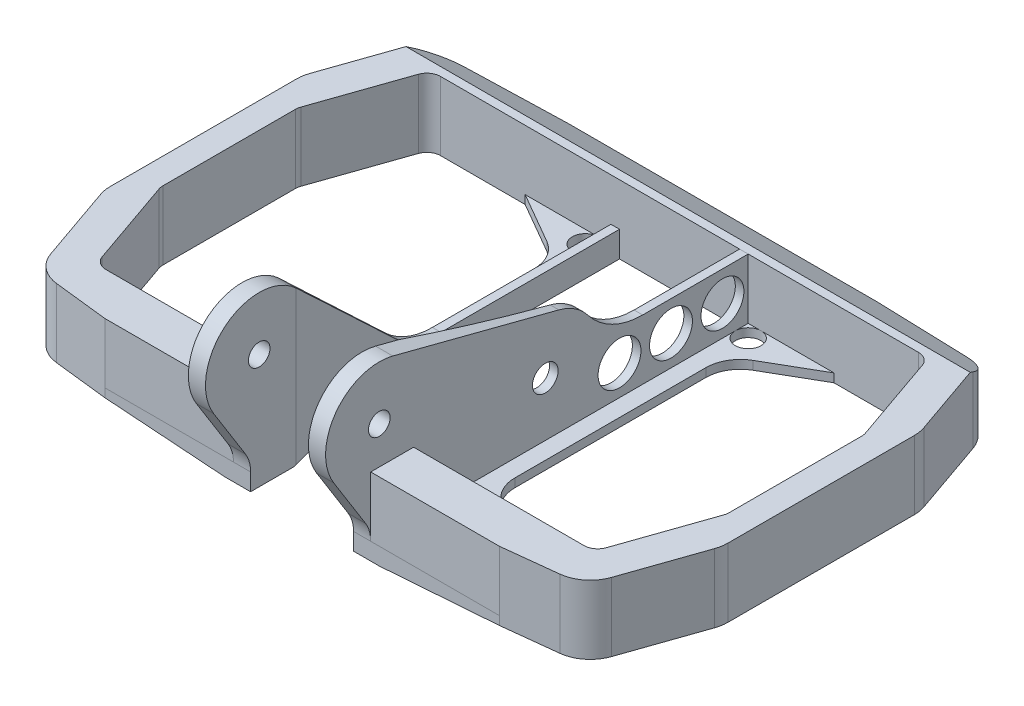
SolidWorks part; units mm, degrees
material "6061 Alloy"
ref_plane "Front Plane" through (0, 0, 0) normal (0, 0, 1) x (1, 0, 0)
ref_plane "Top Plane" through (0, 0, 0) normal (0, 1, 0) x (1, 0, 0)
ref_plane "Right Plane" through (0, 0, 0) normal (1, 0, 0) x (0, 0, -1)
sketch "Sketch1" plane through (0, 0, 0) normal (0, 0, 1) x (1, 0, 0)
  line L0 (19.05, 0) -> (19.05, 76.2)
  line L1 (19.05, 76.2) -> (25.4, 76.2)
  line L2 (25.4, 76.2) -> (25.4, 6.35)
  line L3 (25.4, 6.35) -> (95.25, 6.35)
  line L4 (95.25, 6.35) -> (95.25, 0)
  line L5 (95.25, 0) -> (19.05, 0)
  line L6 (19.05, 0) -> (-19.05, 0) construction
  line L7 (-19.05, 76.2) -> (-19.05, 0)
  line L8 (-19.05, 0) -> (-95.25, 0)
  line L9 (-95.25, 0) -> (-95.25, 6.35)
  line L10 (-95.25, 6.35) -> (-25.4, 6.35)
  line L11 (-25.4, 6.35) -> (-25.4, 76.2)
  line L12 (-25.4, 76.2) -> (-19.05, 76.2)
  point P2 (0, 0)
  dimension "D1" = 76.2
  dimension "D2" = 6.35
  dimension "D3" = 38.1
extrude "Boss-Extrude1" add sketch "Sketch1" against normal blind 203.2
sketch "Sketch4" plane through (25.4, 0, 0) normal (1, 0, 0) x (0, 0, -1)
  line L0 (17.1205, 13.0795) -> (5.3696, 31.8865)
  line L1 (203.2, 0) -> (0, 0) construction
  line L2 (27.2163, 61.6561) -> (88.6811, 45.709)
  line L4 (203.2, 6.35) -> (0, 6.35) construction
  line L5 (19.05, 0) -> (0, 0)
  line L6 (0, 0) -> (0, 76.2)
  line L7 (0, 76.2) -> (203.2, 76.2)
  line L8 (203.2, 76.2) -> (0, 76.2) construction
  line L9 (158.75, 28.575) -> (158.75, 6.35)
  line L10 (158.75, 28.575) -> (103.5343, 28.575)
  line L11 (158.75, 6.35) -> (203.2, 6.35)
  line L12 (203.2, 6.35) -> (203.2, 76.2)
  line L13 (203.2, 0) -> (203.2, 6.35) construction
  line L14 (19.05, 0) -> (19.05, 6.35)
  arc A0 (5.3696, 31.8865) -> (27.2163, 61.6561) centre (22.225, 42.418) cw
  circle A1 centre (22.225, 42.418) radius 4
  circle A2 centre (83.6585, 26.35) radius 20 construction
  arc A3 (88.6811, 45.709) -> (103.5343, 28.575) centre (83.6585, 26.35) cw
  arc A4 (17.1205, 13.0795) -> (19.05, 6.35) centre (6.35, 6.35) cw
  point P27 (19.05, 0)
  point P40 (19.05, 6.35)
  dimension "D1" = 8
  dimension "D3" = 15.875
  dimension "D4" = 40
  dimension "D5" = 63.5
  dimension "D6" = 139.7
  dimension "D9" = 12.7
  dimension "D2" = 42.418
  dimension "D7" = 22.225
  dimension "D8" = 28.575
  dimension "D10" = 3.175
extrude "Cut-Extrude2" cut sketch "Sketch4" against normal through all both and the other way through all
sketch "Sketch7" plane through (-19.05, 0, 0) normal (1, 0, 0) x (0, 0, -1)
  line L0 (17.1205, 13.0795) -> (5.3696, 31.8865)
  line L1 (35.8851, 56.8547) -> (82.55, 12.7)
  line L2 (82.55, 12.7) -> (158.75, 12.7)
  line L3 (158.75, 28.575) -> (158.75, 6.35) construction
  line L4 (158.75, 12.7) -> (158.75, 6.35)
  line L5 (158.75, 6.35) -> (203.2, 6.35)
  line L6 (203.2, 6.35) -> (203.2, 76.2)
  line L7 (203.2, 76.2) -> (0, 76.2)
  line L8 (0, 76.2) -> (0, 0)
  line L9 (0, 0) -> (19.05, 0)
  line L11 (203.2, 0) -> (203.2, 76.2) construction
  line L12 (203.2, 0) -> (203.2, 6.35) construction
  line L13 (203.2, 6.35) -> (19.05, 6.35) construction
  line L14 (19.05, 0) -> (19.05, 6.35) construction
  line L15 (19.05, 0) -> (19.05, 6.35)
  line L16 (103.5343, 28.575) -> (158.75, 28.575) construction
  arc A0 (5.3696, 31.8865) -> (35.8851, 56.8547) centre (22.225, 42.418) cw
  circle A1 centre (22.225, 42.418) radius 4 construction
  circle A2 centre (22.225, 42.418) radius 4
  arc A3 (19.05, 6.35) -> (17.1205, 13.0795) centre (6.35, 6.35) ccw construction
  arc A4 (19.05, 6.35) -> (17.1205, 13.0795) centre (6.35, 6.35) ccw
  dimension "D1" = 76.2
  dimension "D2" = 15.875
extrude "Cut-Extrude4" cut sketch "Sketch7" against normal blind 86.36 and the other way blind 18.542
sketch "Sketch6" plane through (0, 6.35, 0) normal (0, 1, 0) x (1, 0, 0)
  line L0 (73.025, 19.05) -> (73.025, 34.925)
  line L2 (73.025, 34.925) -> (31.75, 58.7551)
  line L3 (31.75, 58.7551) -> (31.75, 144.0853)
  line L4 (31.75, 144.0853) -> (57.15, 158.75)
  line L5 (57.15, 158.75) -> (57.15, 174.625)
  line L7 (95.25, 203.2) -> (95.25, 19.05) construction
  line L8 (95.25, 203.2) -> (95.25, 19.05)
  line L9 (95.25, 19.05) -> (73.025, 19.05)
  line L10 (25.4, 158.75) -> (25.4, 19.05) construction
  line L11 (25.4, 103.5343) -> (25.4, 158.75) construction
  line L12 (0, 0) -> (0, 74.4264) construction
  line L13 (-95.25, 19.05) -> (-73.025, 19.05)
  line L14 (-95.25, 203.2) -> (-95.25, 19.05)
  line L15 (-19.05, 203.2) -> (-95.25, 203.2) construction
  line L16 (-57.15, 158.75) -> (-57.15, 174.625)
  line L17 (-31.75, 144.0853) -> (-57.15, 158.75)
  line L18 (-31.75, 58.7551) -> (-31.75, 144.0853)
  line L19 (-73.025, 34.925) -> (-31.75, 58.7551)
  line L20 (-73.025, 19.05) -> (-73.025, 34.925)
  line L21 (-57.15, 174.625) -> (-19.05, 174.625)
  line L22 (-19.05, 203.2) -> (-19.05, 158.75) construction
  line L23 (-19.05, 174.625) -> (-19.05, 203.2)
  line L24 (-19.05, 203.2) -> (-95.25, 203.2)
  line L25 (57.15, 174.625) -> (19.05, 174.625)
  line L26 (19.05, 203.2) -> (19.05, 158.75) construction
  line L27 (19.05, 174.625) -> (19.05, 203.2)
  line L28 (19.05, 203.2) -> (95.25, 203.2)
  line L29 (19.05, 158.75) -> (25.4, 158.75) construction
  line L30 (-19.05, 158.75) -> (-25.4, 158.75) construction
  line L31 (95.25, 203.2) -> (95.25, 19.05) construction
  dimension "D1" = 47.625
  dimension "D2" = 60
  dimension "D3" = 60
  dimension "D4" = 6.35
  dimension "D5" = 15.875
  dimension "D6" = 31.75
  dimension "D7" = 15.875
extrude "Cut-Extrude3" cut sketch "Sketch6" against normal through all both and the other way through all
sketch "Sketch8" plane through (25.4, 0, 0) normal (1, 0, 0) x (0, 0, -1)
  circle A0 centre (83.6585, 26.35) radius 4.7625
  arc A1 (103.5343, 28.575) -> (88.6811, 45.709) centre (83.6585, 26.35) ccw construction
  dimension "D1" = 9.525
extrude "Cut-Extrude5" cut sketch "Sketch8" against normal through all
fillet "Fillet1" radius 25.4 1 edges at (22.225, 28.575, -103.5343)
fillet "Fillet2" radius 25.4 1 edges at (-22.225, 12.7, -82.55)
sketch "Sketch11" plane through (31.75, 0, 0) normal (1, 0, 0) x (0, 0, -1)
  line L0 (174.625, 3.175) -> (58.7551, 3.175)
  line L1 (174.625, 0) -> (174.625, 6.35) construction
  line L2 (58.7551, 0) -> (58.7551, 6.35) construction
  arc A0 (58.7551, 3.175) -> (34.925, 0) centre (58.7551, -87.8417) ccw
extrude "Cut-Extrude7" cut sketch "Sketch11" against normal through all both and the other way through all
sketch "Sketch13" plane through (0, 6.35, 0) normal (0, 1, 0) x (1, 0, 0)
  line L0 (-22.225, 174.625) -> (-22.225, 92.6622)
  line L1 (-19.05, 34.925) -> (-19.05, 58.7551) construction
  line L2 (-19.05, 158.75) -> (-25.4, 158.75) construction
  line L3 (-57.15, 174.625) -> (-19.05, 174.625) construction
  line L4 (-25.4, 92.6622) -> (-19.05, 92.6622) construction
  line L6 (-19.05, 75.2048) -> (-19.05, 35.8851) construction
  line L7 (-22.225, 174.625) -> (22.225, 174.625)
  line L8 (19.05, 174.625) -> (57.15, 174.625) construction
  line L9 (22.225, 174.625) -> (22.225, 92.6622)
  line L10 (19.05, 35.8851) -> (-19.05, 35.8851)
  line L11 (19.05, 88.6811) -> (19.05, 27.2163) construction
  line L12 (19.05, 158.75) -> (25.4, 158.75) construction
  arc A0 (-22.225, 92.6622) -> (-19.05, 35.8851) centre (487.0223, 92.6622) ccw
  arc A1 (22.225, 92.6622) -> (19.05, 35.8851) centre (-487.0223, 92.6622) cw
  point P11 (-22.225, 158.75)
  point P31 (22.225, 158.75)
extrude "Cut-Extrude8" cut sketch "Sketch13" against normal through all both and the other way through all
sketch "Sketch19" plane through (0, 3.175, 0) normal (0, -1, 0) x (1, 0, 0)
  line L0 (-57.15, -174.625) -> (57.15, -174.625)
  line L1 (-101.1039, -171.45) -> (-114.3, -133.5113)
  line L2 (-114.3, -133.5113) -> (-114.3, -60.1637)
  line L3 (-114.3, -60.1637) -> (-101.1039, -22.225)
  line L4 (-73.025, -19.05) -> (-25.4, -19.05)
  line L5 (101.1039, -22.225) -> (114.3, -60.1637)
  line L6 (114.3, -60.1637) -> (114.3, -133.5113)
  line L7 (114.3, -133.5113) -> (101.1039, -171.45)
  line L8 (-19.05, -19.05) -> (-73.025, -19.05) construction
  line L9 (-25.4, -19.05) -> (-25.4, -34.925)
  line L10 (-25.4, -34.925) -> (-92.075, -34.925)
  line L11 (25.4, -19.05) -> (25.4, -34.925)
  line L12 (25.4, -34.925) -> (92.075, -34.925)
  line L13 (25.4, -19.05) -> (73.025, -19.05)
  line L14 (-19.05, -34.925) -> (-73.025, -34.925) construction
  line L15 (73.025, -34.925) -> (19.05, -34.925) construction
  line L16 (19.05, -19.05) -> (73.025, -19.05) construction
  line L17 (25.4, -17.1205) -> (25.4, -5.3696) construction
  line L18 (-25.4, -17.1205) -> (-25.4, -5.3696) construction
  line L19 (92.075, -34.925) -> (104.775, -71.4375)
  line L20 (104.775, -71.4375) -> (104.775, -122.2375)
  line L21 (104.775, -122.2375) -> (92.075, -158.75)
  line L22 (92.075, -158.75) -> (-92.075, -158.75)
  line L23 (-92.075, -158.75) -> (-104.775, -122.2375)
  line L24 (-104.775, -122.2375) -> (-104.775, -71.4375)
  line L25 (-104.775, -71.4375) -> (-92.075, -34.925)
  line L26 (-57.15, -174.625) -> (-101.1039, -171.45)
  line L27 (57.15, -174.625) -> (101.1039, -171.45)
  line L28 (73.025, -19.05) -> (101.1039, -22.225)
  line L29 (-73.025, -19.05) -> (-101.1039, -22.225)
  point P33 (-25.4, -11.2451)
  dimension "D1" = 228.6
  dimension "D2" = 3.175
  dimension "D3" = 12.7
  dimension "D4" = 50.8
  dimension "D5" = 9.525
  dimension "D6" = 12.7
  dimension "D7" = 9.525
  dimension "D8" = 12.7
  dimension "D9" = 3.175
extrude "Boss-Extrude2" add sketch "Sketch19" against normal blind 25.4 separate body
sketch "Sketch20" plane through (0, 3.175, 0) normal (0, -1, 0) x (1, 0, 0)
  line L0 (22.225, -174.625) -> (22.225, -92.6622) construction
  line L1 (-73.025, -19.05) -> (73.025, -19.05)
  line L2 (-73.025, -19.05) -> (-73.025, -34.925)
  line L3 (-73.025, -34.925) -> (73.025, -34.925)
  line L4 (73.025, -19.05) -> (73.025, -34.925)
  line L5 (22.225, -158.75) -> (57.15, -158.75)
  line L6 (22.225, -158.75) -> (22.225, -174.625)
  line L7 (22.225, -174.625) -> (57.15, -174.625)
  line L8 (57.15, -158.75) -> (57.15, -174.625)
  line L10 (-57.15, -174.625) -> (-22.225, -174.625)
  line L11 (-57.15, -174.625) -> (-57.15, -158.75)
  line L12 (-57.15, -158.75) -> (-22.225, -158.75)
  line L13 (-22.225, -174.625) -> (-22.225, -158.75)
  line L14 (-22.225, -92.6622) -> (-22.225, -174.625) construction
  line L15 (92.075, -158.75) -> (-92.075, -158.75) construction
  line L16 (-31.75, -144.0853) -> (-57.15, -158.75) construction
  point P17 (-57.15, -174.625)
  point P21 (0, 0)
extrude "Cut-Extrude14" cut sketch "Sketch20" against normal blind 3.175
sketch "Sketch21" plane through (0, 0, -19.05) normal (0, 0, 1) x (1, 0, 0)
  line L0 (73.025, 3.175) -> (28.575, 0)
  line L1 (19.05, 0) -> (73.025, 0) construction
  line L2 (28.575, 0) -> (-28.575, 0)
  line L3 (-19.05, 0) -> (-73.025, 0) construction
  line L4 (-28.575, 0) -> (-73.025, 3.175)
  line L5 (-73.025, 0) -> (-73.025, 6.35) construction
  line L6 (-73.025, 3.175) -> (-73.025, -19.7401)
  line L7 (-73.025, -19.7401) -> (73.025, -19.7401)
  line L8 (73.025, -19.7401) -> (73.025, 3.175)
  point P5 (0, 0)
  point P14 (73.025, 3.175)
  dimension "D1" = 57.15
extrude "Cut-Extrude15" cut sketch "Sketch21" against normal through all both and the other way through all
sketch "Sketch22" plane through (25.4, 0, 0) normal (1, 0, 0) x (0, 0, -1)
  line L0 (158.75, 28.575) -> (158.75, 6.35) construction
  circle A0 centre (149.225, 17.4625) radius 7.9375
  circle A1 centre (130.175, 17.4625) radius 7.9375
  circle A2 centre (111.125, 17.4625) radius 7.9375
  circle A4 centre (92.075, 17.4625) radius 7.9375 [skipped]
  point P10 (158.75, 17.4625)
  dimension "D1" = 4
  dimension "D2" = 15.875
  dimension "D3" = 19.05
  dimension "D4" = 9.525
extrude "Cut-Extrude16" cut sketch "Sketch22" against normal blind 3.175
sketch "Sketch23" plane through (0, 6.35, 0) normal (0, 1, 0) x (1, 0, 0)
  line L0 (25.4, 34.925) -> (92.075, 34.925) construction
  line L1 (25.4, 27.2163) -> (25.4, 88.6811) construction
  line L2 (0, 0) -> (0, 104.0299) construction
  line L3 (57.15, 158.75) -> (22.225, 158.75) construction
  line L4 (25.4, 119.6865) -> (25.4, 158.75) construction
  circle A0 centre (33.3375, 42.8625) radius 7.9375
  circle A1 centre (48.4244, 39.6875) radius 4.7625
  circle A2 centre (-48.4244, 39.6875) radius 4.7625
  circle A3 centre (-33.3375, 42.8625) radius 7.9375
  circle A4 centre (30.1625, 153.9875) radius 4.7625
  circle A5 centre (-30.1625, 153.9875) radius 4.7625
  dimension "D1" = 15.875
  dimension "D2" = 9.525
  dimension "D3" = 9.525
extrude "Cut-Extrude17" cut sketch "Sketch23" against normal through all
chamfer "Chamfer1" distance 12.7 angle 30 1 edges at (0, 28.575, -174.625) first distance on face at (0, 28.575, -85.1958)
fillet "Fillet3" radius 5.08 8 edges at (-92.075, 15.875, -158.75) (-104.775, 15.875, -122.2375) (-104.775, 15.875, -71.4375) (-92.075, 15.875, -34.925) (92.075, 15.875, -158.75) (104.775, 15.875, -122.2375) (104.775, 15.875, -71.4375) (92.075, 15.875, -34.925)
fillet "Fillet4" radius 12.7 8 edges at (-101.1039, 15.875, -22.225) (-114.3, 15.875, -60.1637) (-114.3, 15.875, -133.5113) (-101.1039, 13.1254, -171.45) (101.1039, 15.875, -22.225) (114.3, 15.875, -60.1637) (114.3, 15.875, -133.5113) (101.1039, 13.1254, -171.45)
fillet "Fillet5" radius 12.7 2 edges at (31.75, 4.7625, -144.0853) (31.75, 4.7625, -58.7551)
fillet "Fillet6" radius 12.7 2 edges at (-31.75, 4.7625, -144.0853) (-31.75, 4.7625, -58.7551)
